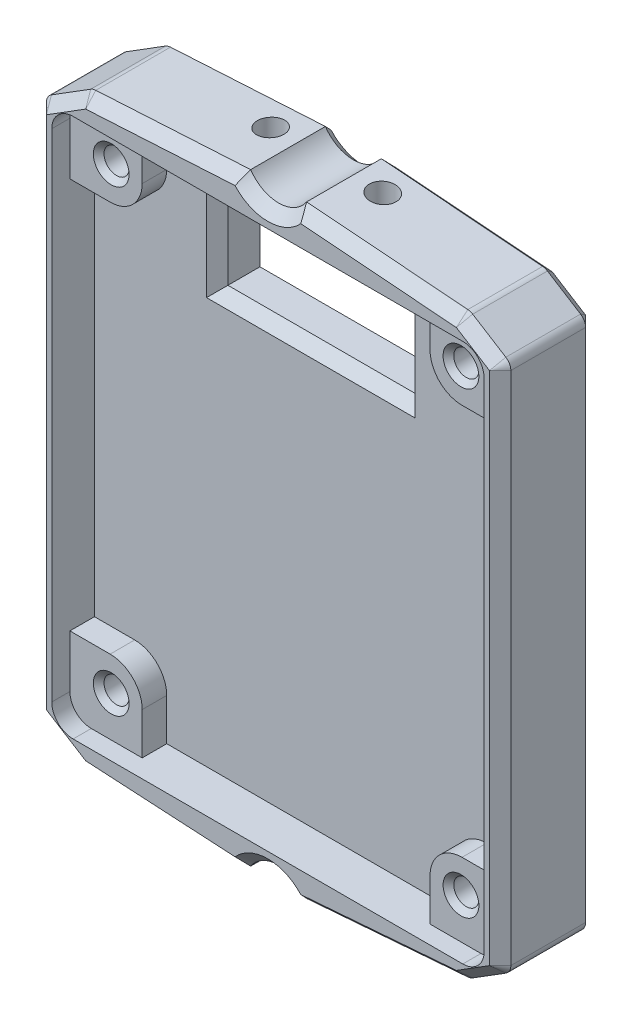
SolidWorks part; units mm, degrees
ref_plane "Front Plane" through (0, 0, 0) normal (0, 0, 1) x (1, 0, 0)
ref_plane "Top Plane" through (0, 0, 0) normal (0, 1, 0) x (1, 0, 0)
ref_plane "Right Plane" through (0, 0, 0) normal (1, 0, 0) x (0, 0, -1)
sketch "Sketch1" plane through (0, 0, 0) normal (0, 0, 1) x (1, 0, 0)
  line L0 (-23.25, 28.25) -> (-23.25, -28.25)
  line L1 (-20.25, 25.25) -> (20.25, 25.25)
  line L2 (-20.25, 25.25) -> (-20.25, -25.25)
  line L3 (-20.25, -25.25) -> (20.25, -25.25)
  line L4 (20.25, 25.25) -> (20.25, -25.25)
  line L5 (-20.25, 25.25) -> (20.25, -25.25) construction
  line L6 (-20.25, -25.25) -> (20.25, 25.25) construction
  line L7 (-23.25, -28.25) -> (23.25, -28.25)
  line L8 (23.25, 28.25) -> (23.25, -28.25)
  line L9 (-23.25, 28.25) -> (23.25, 28.25)
  point P0 (0, 0)
  dimension "D1" = 50.5
  dimension "D2" = 40.5
  dimension "D3" = 3
extrude "Boss-Extrude1" add sketch "Sketch1" along normal blind 4
sketch "Sketch2" plane through (0, 0, 0) normal (0, 0, -1) x (-1, 0, 0)
  line L1 (-23.25, 28.25) -> (23.25, 28.25)
  line L2 (-23.25, 28.25) -> (-23.25, -28.25)
  line L3 (-23.25, -28.25) -> (23.25, -28.25)
  line L4 (23.25, 28.25) -> (23.25, -28.25)
extrude "Boss-Extrude2" add sketch "Sketch2" along normal blind 5
sketch "Sketch3" plane through (0, 0, 0) normal (0, 0, 1) x (1, 0, 0)
  line L0 (0, 0) -> (0, 30.8352) construction
  line L1 (0, 0) -> (-31.9704, 0) construction
  line L2 (-20.25, 25.25) -> (-20.25, 18.3322)
  line L3 (-20.25, 25.25) -> (-20.25, -25.25) construction
  line L4 (-20.25, 18.3322) -> (-13.4806, 18.3322)
  line L5 (-13.4806, 18.3322) -> (-13.4806, 25.25)
  line L6 (20.25, 25.25) -> (-20.25, 25.25) construction
  line L7 (-13.4806, 25.25) -> (-20.25, 25.25)
  line L8 (13.4806, 25.25) -> (20.25, 25.25)
  line L9 (13.4806, 18.3322) -> (13.4806, 25.25)
  line L10 (20.25, 18.3322) -> (13.4806, 18.3322)
  line L11 (20.25, 25.25) -> (20.25, 18.3322)
  line L12 (20.25, -25.25) -> (20.25, -18.3322)
  line L13 (20.25, -18.3322) -> (13.4806, -18.3322)
  line L14 (13.4806, -18.3322) -> (13.4806, -25.25)
  line L15 (13.4806, -25.25) -> (20.25, -25.25)
  line L16 (-13.4806, -25.25) -> (-20.25, -25.25)
  line L17 (-13.4806, -18.3322) -> (-13.4806, -25.25)
  line L18 (-20.25, -18.3322) -> (-13.4806, -18.3322)
  line L19 (-20.25, -25.25) -> (-20.25, -18.3322)
  circle A0 centre (-16.38, 21.46) radius 1.175
  circle A1 centre (16.38, 21.46) radius 1.175
  circle A2 centre (16.38, -21.46) radius 1.175
  circle A3 centre (-16.38, -21.46) radius 1.175
  dimension "D3" = 2.35
  dimension "D1" = 21.46
  dimension "D2" = 16.38
extrude "Boss-Extrude3" add sketch "Sketch3" along normal blind 2.3
chamfer "Chamfer3" distance 4.5 angle 58 4 edges at (-23.25, -28.25, -0.5) (23.25, -28.25, -0.5) (-23.25, 28.25, -0.5) (23.25, 28.25, -0.5) first distance on face at (-23.25, 0, -0.5) first distance on face at (23.25, 0, -0.5)
fillet "Fillet1" radius 3 4 edges at (13.4806, -18.3322, 1.15) (-13.4806, -18.3322, 1.15) (13.4806, 18.3322, 1.15) (-13.4806, 18.3322, 1.15)
sketch "Sketch4" plane through (0, 0, 0) normal (0, 0, 1) x (1, 0, 0)
  line L0 (20.25, 25.25) -> (-20.25, 25.25) construction
  line L1 (-8.75, 23.8) -> (8.75, 23.8)
  line L2 (-8.75, 23.8) -> (-8.75, 13.8)
  line L3 (-8.75, 13.8) -> (8.75, 13.8)
  line L4 (8.75, 23.8) -> (8.75, 13.8)
  point P4 (0, 13.8)
  dimension "D1" = 10
  dimension "D2" = 1.45
  dimension "D3" = 17.5
extrude "Cut-Extrude1" cut sketch "Sketch4" against normal through all
sketch "Sketch5" plane through (0, 0, -5) normal (0, 0, -1) x (-1, 0, 0)
  line L0 (-29.5901, 0) -> (35.962, 0) construction
  line L4 (0, 42.4173) -> (0, 14.6256) construction
  line L8 (-23.25, -28.25) -> (23.25, -28.25)
  line L9 (23.25, -28.25) -> (23.25, -27.0847)
  line L10 (23.25, -27.0847) -> (2.6192, -28.25)
  line L11 (-23.25, -26.638) -> (-2.6192, -28.25)
  line L12 (-23.25, -28.25) -> (-23.25, -26.638)
  line L14 (16.0485, 28.25) -> (-16.0485, 28.25) construction
  line L15 (-2.6192, 28.25) -> (2.6192, 28.25)
  line L16 (-23.25, 28.25) -> (-23.25, 26.638)
  line L17 (-23.25, 26.638) -> (-2.6192, 28.25)
  line L18 (23.25, 27.0847) -> (2.6192, 28.25)
  line L19 (23.25, 28.25) -> (23.25, 27.0847)
  line L20 (-23.25, 28.25) -> (23.25, 28.25)
  arc A0 (-2.6192, 28.25) -> (2.6192, 28.25) centre (0, 30) ccw
  arc A1 (-2.6192, -28.25) -> (2.6192, -28.25) centre (0, -30) cw
  point P12 (0, 0)
  point P13 (-23.25, 26.638)
  line M10 (-16.0485, -28.25) -> (16.0485, -28.25)
  line M12 (16.0485, 28.25) -> (-16.0485, 28.25)
  line M22 (16.0485, -28.25) -> (23.25, -23.75)
  line M23 (23.25, 23.75) -> (16.0485, 28.25)
  line M24 (-16.0485, 28.25) -> (-23.25, 23.75)
  line M25 (-23.25, -23.75) -> (-16.0485, -28.25)
  dimension "D1" = 6.3
  dimension "D3" = 60
extrude "Cut-Extrude2" cut sketch "Sketch5" against normal through all contours L12 L8 L11 M25 | A1 L8 | L9 L10 L8 M22 | L11 M25 M10 | L10 L8 M22 | L17 M24 M12 | L18 M23 M12 | L20 L18 L19 M23 | L20 L16 L17 M24 | A0 M12 | L11 A1 L10 L9 L8 L12 region at (20.2805, -27.5835, -5) region at (-12.0169, -27.972, -5) region at (0, -27.6777, -5) region at (12.2118, -27.8502, -5) region at (-20.1718, -27.7652, -5) region at (-12.0169, 27.972, -5) region at (12.2118, 27.8502, -5) region at (0, 27.6777, -5) region at (20.2805, 27.5835, -5) region at (-20.1718, 27.7652, -5)
sketch "Sketch6" plane through (0, 0, 4) normal (0, 0, 1) x (1, 0, 0)
  line L0 (-17.3831, -27.4161) -> (-2.6192, -28.25) construction
  line L1 (-23.2503, 33.2078) -> (-21.7503, 33.2078)
  line L2 (-23.2503, 33.2078) -> (-23.2503, -27.1694)
  line L3 (-23.2503, -27.1694) -> (-21.7503, -27.1694)
  line L4 (-21.7503, 33.2078) -> (-21.7503, -27.1694)
  line L5 (0, 0) -> (0, 31.5361) construction
  line L6 (21.7503, 33.2078) -> (21.7503, -27.1694)
  line L7 (23.2503, -27.1694) -> (21.7503, -27.1694)
  line L8 (23.2503, 33.2078) -> (23.2503, -27.1694)
  line L9 (23.2503, 33.2078) -> (21.7503, 33.2078)
  point P14 (0, 0)
  point P15 (-21.7503, 33.2078)
  dimension "D1" = 1.5
extrude "Cut-Extrude3" cut sketch "Sketch6" against normal through all
sketch "Sketch7" plane through (0, 0, 0) normal (0, 1, 0) x (1, 0, 0)
  line L0 (-5.25, 1.5) -> (5.25, 1.5) construction
  line L1 (2.6192, 5) -> (-2.6192, 5) construction
  circle A0 centre (-5.25, 1.5) radius 1.25
  circle A1 centre (5.25, 1.5) radius 1.25
  point P4 (0, 1.5)
  dimension "D1" = 2.5
  dimension "D2" = 10.5
  dimension "D3" = 3.5
extrude "Cut-Extrude4" cut sketch "Sketch7" against normal blind 10 from offset 30
mirror "Mirror1" about plane through (0, 0, 0) normal (0, 1, 0) of "Cut-Extrude4"
fillet "Fillet2" radius 1 8 edges at (21.7503, -24.6871, -0.5) (17.9677, -27.0507, -0.5) (-17.3831, -27.4161, -0.5) (-21.7503, -24.6871, -0.5) (-21.7503, 24.6871, -0.5) (21.7503, 24.6871, -0.5) (-17.3831, 27.4161, -0.5) (17.9677, 27.0507, -0.5)
chamfer "Chamfer1" distance 1 angle 45 48 edges at (0, -26.85, 4) (0, 26.85, 4) (-9.8731, -27.8403, 4) (-21.7503, 0, 4) (10.1713, -27.6599, 4) (21.7503, 0, 4) (0, 23.8, 0) (-8.75, 18.8, 0) (8.75, 18.8, 0) (0, 13.8, 0) (0, 26.85, -5) (8.75, 18.8, -5) (0, 13.8, -5) (-8.75, 18.8, -5) (0, 23.8, -5) (-21.7503, 0, -5) (21.7503, 0, -5) (-9.8731, -27.8403, -5) (0, -26.85, -5) (10.1713, -27.6599, -5) (-17.3733, -27.3852, 4) (-19.4404, -26.1305, 4) (-19.4404, 26.1305, 4) (-21.6249, -24.6176, 4) (-21.6249, 24.6176, 4) (17.9585, -27.0226, 4) (19.7279, 25.9509, 4) (19.7279, -25.9509, 4) (21.6249, 24.6176, 4) (21.6249, -24.6176, 4) (-19.4404, 26.1305, -5) (19.7279, 25.9509, -5) (-21.6249, 24.6176, -5) (21.6249, 24.6176, -5) (-21.6249, -24.6176, -5) (21.6249, -24.6176, -5) (-19.4404, -26.1305, -5) (19.7279, -25.9509, -5) (-17.3733, -27.3852, -5) (17.9585, -27.0226, -5) (-9.8731, 27.8403, 4) (-17.3733, 27.3852, 4) (10.1713, 27.6599, 4) (17.9585, 27.0226, 4) (-9.8731, 27.8403, -5) (10.1713, 27.6599, -5) (-17.3733, 27.3852, -5) (17.9585, 27.0226, -5)
fillet "Fillet3" radius 2 4 edges at (-20.25, -25.25, 2.8088) (20.25, -25.25, 2.8088) (20.25, 25.25, 2.8088) (-20.25, 25.25, 2.8088)
sketch "Sketch8" plane through (0, 0, 2.3) normal (0, 0, 1) x (1, 0, 0)
  circle A0 centre (-16.38, 21.46) radius 1.175
  circle A1 centre (16.38, 21.46) radius 1.175
  circle A2 centre (16.38, -21.46) radius 1.175
  circle A3 centre (-16.38, -21.46) radius 1.175
  circle A4 centre (-16.38, 21.46) radius 1.175 construction
extrude "Cut-Extrude5" cut sketch "Sketch8" against normal through all
sketch "Sketch9" plane through (0, 0, -5) normal (0, 0, -1) x (-1, 0, 0)
  line L0 (0, 9.9819) -> (0, -23.9909) construction
  line L1 (-16.3742, -2.0365) -> (-6.3848, -2.0365)
  line L2 (-12.6187, -3.5365) -> (-6.3848, -3.5365)
  line L3 (-16.3742, -2.0365) -> (0, -17.5995)
  line L4 (-12.6187, -3.5365) -> (0, -15.5301)
  line L5 (-4, -2.7865) -> (-12.6323, -2.7865) construction
  line L6 (12.6187, -3.5365) -> (0, -15.5301)
  line L7 (16.3742, -2.0365) -> (0, -17.5995)
  line L8 (12.6187, -3.5365) -> (6.3848, -3.5365)
  line L9 (16.3742, -2.0365) -> (6.3848, -2.0365)
  arc A0 (-6.3848, -3.5365) -> (-6.3848, -2.0365) centre (-4, -2.7865) ccw
  arc A1 (6.3848, -3.5365) -> (6.3848, -2.0365) centre (4, -2.7865) cw
  point P4 (0, -10.7426)
  point P9 (-10.6467, 4.455)
  point P11 (-3.6329, 5.074)
  point P14 (0, -7.8115)
  point P20 (0, -8.8937)
  point P21 (-4.0368, 5.3634)
  point P22 (-16.7591, 6.048)
  point P23 (0, 0)
  point P24 (0, 0)
  point P25 (0, 0)
  point P26 (0, 18.0664)
  dimension "D1" = 5
  dimension "D2" = 1.5
  dimension "D3" = 1.5
  dimension "D4" = 8
extrude "Cut-Extrude6" cut sketch "Sketch9" against normal blind 1
chamfer "Chamfer2" distance 0.5 angle 45 4 edges at (-17.555, -21.46, 2.3) (17.555, -21.46, 2.3) (15.205, 21.46, 2.3) (-15.205, 21.46, 2.3)
